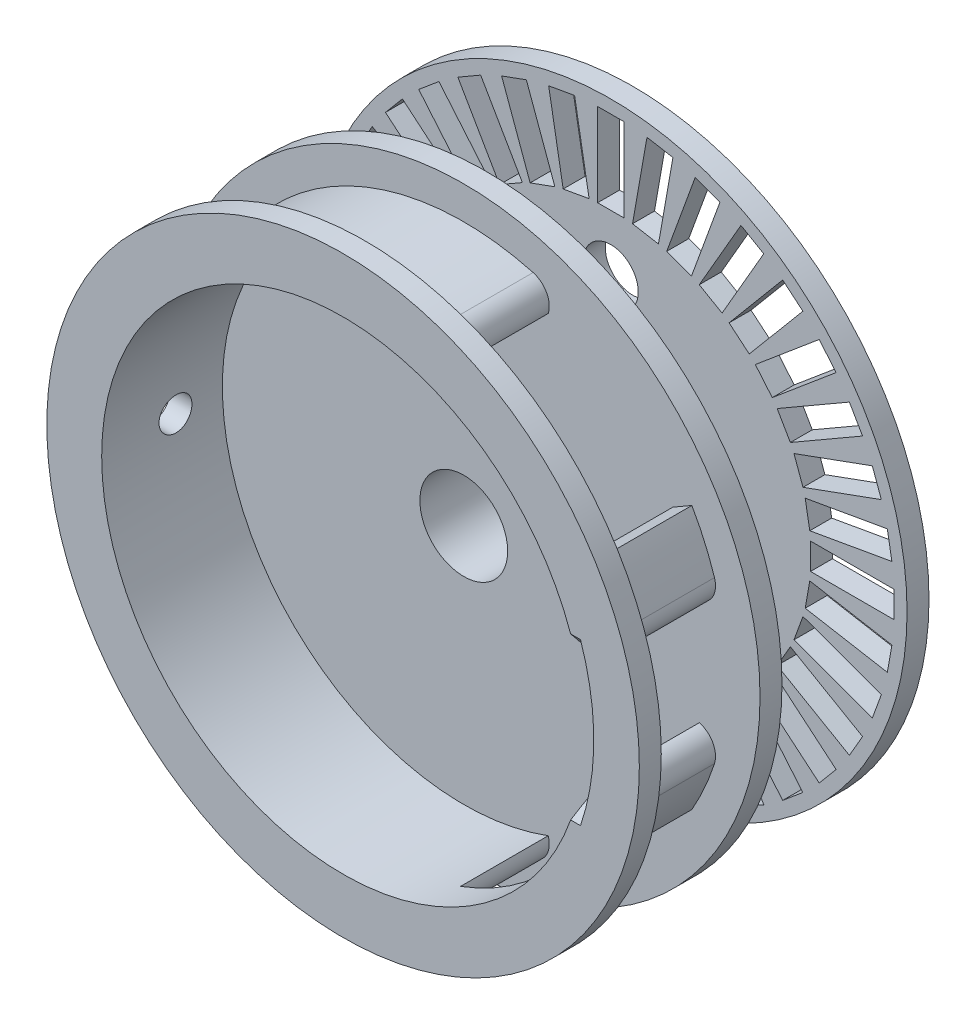
SolidWorks part; units mm, degrees
ref_plane "Front Plane" through (0, 0, 0) normal (0, 0, 1) x (1, 0, 0)
ref_plane "Top Plane" through (0, 0, 0) normal (0, 1, 0) x (1, 0, 0)
ref_plane "Right Plane" through (0, 0, 0) normal (1, 0, 0) x (0, 0, -1)
sketch "Sketch1" plane through (0, 0, 0) normal (0, 0, 1) x (1, 0, 0)
  line L0 (2.1711, 8.8576) -> (0.9893, 9.0659)
  line L1 (0.6, 9.1) -> (-0.6, 9.1)
  line L2 (0.6, 9.1) -> (0.6, 12.9)
  line L3 (0.6, 12.9) -> (-0.6, 12.9)
  line L4 (-0.6, 9.1) -> (-0.6, 12.9)
  line L5 (0.6, 9.1) -> (-0.6, 12.9) construction
  line L6 (0.6, 12.9) -> (-0.6, 9.1) construction
  line L7 (0.9893, 9.0659) -> (1.6492, 12.8082)
  line L8 (2.1711, 8.8576) -> (2.8309, 12.5998)
  line L9 (2.8309, 12.5998) -> (1.6492, 12.8082)
  line L10 (3.6762, 8.346) -> (2.5486, 8.7564)
  line L11 (2.5486, 8.7564) -> (3.8482, 12.3272)
  line L12 (3.6762, 8.346) -> (4.9759, 11.9168)
  line L13 (4.9759, 11.9168) -> (3.8482, 12.3272)
  line L14 (5.0696, 7.5808) -> (4.0304, 8.1808)
  line L15 (4.0304, 8.1808) -> (5.9304, 11.4717)
  line L16 (5.0696, 7.5808) -> (6.9696, 10.8717)
  line L17 (6.9696, 10.8717) -> (5.9304, 11.4717)
  line L18 (6.309, 6.5853) -> (5.3897, 7.3567)
  line L19 (5.3897, 7.3567) -> (7.8323, 10.2676)
  line L20 (6.309, 6.5853) -> (8.7516, 9.4963)
  line L21 (8.7516, 9.4963) -> (7.8323, 10.2676)
  line L22 (7.3567, 5.3897) -> (6.5853, 6.309)
  line L23 (6.5853, 6.309) -> (9.4963, 8.7516)
  line L24 (7.3567, 5.3897) -> (10.2676, 7.8323)
  line L25 (10.2676, 7.8323) -> (9.4963, 8.7516)
  line L26 (8.1808, 4.0304) -> (7.5808, 5.0696)
  line L27 (7.5808, 5.0696) -> (10.8717, 6.9696)
  line L28 (8.1808, 4.0304) -> (11.4717, 5.9304)
  line L29 (11.4717, 5.9304) -> (10.8717, 6.9696)
  line L30 (8.7564, 2.5486) -> (8.346, 3.6762)
  line L31 (8.346, 3.6762) -> (11.9168, 4.9759)
  line L32 (8.7564, 2.5486) -> (12.3272, 3.8482)
  line L33 (12.3272, 3.8482) -> (11.9168, 4.9759)
  line L34 (9.0659, 0.9893) -> (8.8576, 2.1711)
  line L35 (8.8576, 2.1711) -> (12.5998, 2.8309)
  line L36 (9.0659, 0.9893) -> (12.8082, 1.6492)
  line L37 (12.8082, 1.6492) -> (12.5998, 2.8309)
  line L38 (9.1, -0.6) -> (9.1, 0.6)
  line L39 (9.1, 0.6) -> (12.9, 0.6)
  line L40 (9.1, -0.6) -> (12.9, -0.6)
  line L41 (12.9, -0.6) -> (12.9, 0.6)
  line L42 (8.8576, -2.1711) -> (9.0659, -0.9893)
  line L43 (9.0659, -0.9893) -> (12.8082, -1.6492)
  line L44 (8.8576, -2.1711) -> (12.5998, -2.8309)
  line L45 (12.5998, -2.8309) -> (12.8082, -1.6492)
  line L46 (8.346, -3.6762) -> (8.7564, -2.5486)
  line L47 (8.7564, -2.5486) -> (12.3272, -3.8482)
  line L48 (8.346, -3.6762) -> (11.9168, -4.9759)
  line L49 (11.9168, -4.9759) -> (12.3272, -3.8482)
  line L50 (7.5808, -5.0696) -> (8.1808, -4.0304)
  line L51 (8.1808, -4.0304) -> (11.4717, -5.9304)
  line L52 (7.5808, -5.0696) -> (10.8717, -6.9696)
  line L53 (10.8717, -6.9696) -> (11.4717, -5.9304)
  line L54 (6.5853, -6.309) -> (7.3567, -5.3897)
  line L55 (7.3567, -5.3897) -> (10.2676, -7.8323)
  line L56 (6.5853, -6.309) -> (9.4963, -8.7516)
  line L57 (9.4963, -8.7516) -> (10.2676, -7.8323)
  line L58 (5.3897, -7.3567) -> (6.309, -6.5853)
  line L59 (6.309, -6.5853) -> (8.7516, -9.4963)
  line L60 (5.3897, -7.3567) -> (7.8323, -10.2676)
  line L61 (7.8323, -10.2676) -> (8.7516, -9.4963)
  line L62 (4.0304, -8.1808) -> (5.0696, -7.5808)
  line L63 (5.0696, -7.5808) -> (6.9696, -10.8717)
  line L64 (4.0304, -8.1808) -> (5.9304, -11.4717)
  line L65 (5.9304, -11.4717) -> (6.9696, -10.8717)
  line L66 (2.5486, -8.7564) -> (3.6762, -8.346)
  line L67 (3.6762, -8.346) -> (4.9759, -11.9168)
  line L68 (2.5486, -8.7564) -> (3.8482, -12.3272)
  line L69 (3.8482, -12.3272) -> (4.9759, -11.9168)
  line L70 (0.9893, -9.0659) -> (2.1711, -8.8576)
  line L71 (2.1711, -8.8576) -> (2.8309, -12.5998)
  line L72 (0.9893, -9.0659) -> (1.6492, -12.8082)
  line L73 (1.6492, -12.8082) -> (2.8309, -12.5998)
  line L74 (-0.6, -9.1) -> (0.6, -9.1)
  line L75 (0.6, -9.1) -> (0.6, -12.9)
  line L76 (-0.6, -9.1) -> (-0.6, -12.9)
  line L77 (-0.6, -12.9) -> (0.6, -12.9)
  line L78 (-2.1711, -8.8576) -> (-0.9893, -9.0659)
  line L79 (-0.9893, -9.0659) -> (-1.6492, -12.8082)
  line L80 (-2.1711, -8.8576) -> (-2.8309, -12.5998)
  line L81 (-2.8309, -12.5998) -> (-1.6492, -12.8082)
  line L82 (-3.6762, -8.346) -> (-2.5486, -8.7564)
  line L83 (-2.5486, -8.7564) -> (-3.8482, -12.3272)
  line L84 (-3.6762, -8.346) -> (-4.9759, -11.9168)
  line L85 (-4.9759, -11.9168) -> (-3.8482, -12.3272)
  line L86 (-5.0696, -7.5808) -> (-4.0304, -8.1808)
  line L87 (-4.0304, -8.1808) -> (-5.9304, -11.4717)
  line L88 (-5.0696, -7.5808) -> (-6.9696, -10.8717)
  line L89 (-6.9696, -10.8717) -> (-5.9304, -11.4717)
  line L90 (-6.309, -6.5853) -> (-5.3897, -7.3567)
  line L91 (-5.3897, -7.3567) -> (-7.8323, -10.2676)
  line L92 (-6.309, -6.5853) -> (-8.7516, -9.4963)
  line L93 (-8.7516, -9.4963) -> (-7.8323, -10.2676)
  line L94 (-7.3567, -5.3897) -> (-6.5853, -6.309)
  line L95 (-6.5853, -6.309) -> (-9.4963, -8.7516)
  line L96 (-7.3567, -5.3897) -> (-10.2676, -7.8323)
  line L97 (-10.2676, -7.8323) -> (-9.4963, -8.7516)
  line L98 (-8.1808, -4.0304) -> (-7.5808, -5.0696)
  line L99 (-7.5808, -5.0696) -> (-10.8717, -6.9696)
  line L100 (-8.1808, -4.0304) -> (-11.4717, -5.9304)
  line L101 (-11.4717, -5.9304) -> (-10.8717, -6.9696)
  line L102 (-8.7564, -2.5486) -> (-8.346, -3.6762)
  line L103 (-8.346, -3.6762) -> (-11.9168, -4.9759)
  line L104 (-8.7564, -2.5486) -> (-12.3272, -3.8482)
  line L105 (-12.3272, -3.8482) -> (-11.9168, -4.9759)
  line L106 (-9.0659, -0.9893) -> (-8.8576, -2.1711)
  line L107 (-8.8576, -2.1711) -> (-12.5998, -2.8309)
  line L108 (-9.0659, -0.9893) -> (-12.8082, -1.6492)
  line L109 (-12.8082, -1.6492) -> (-12.5998, -2.8309)
  line L110 (-9.1, 0.6) -> (-9.1, -0.6)
  line L111 (-9.1, -0.6) -> (-12.9, -0.6)
  line L112 (-9.1, 0.6) -> (-12.9, 0.6)
  line L113 (-12.9, 0.6) -> (-12.9, -0.6)
  line L114 (-8.8576, 2.1711) -> (-9.0659, 0.9893)
  line L115 (-9.0659, 0.9893) -> (-12.8082, 1.6492)
  line L116 (-8.8576, 2.1711) -> (-12.5998, 2.8309)
  line L117 (-12.5998, 2.8309) -> (-12.8082, 1.6492)
  line L118 (-8.346, 3.6762) -> (-8.7564, 2.5486)
  line L119 (-8.7564, 2.5486) -> (-12.3272, 3.8482)
  line L120 (-8.346, 3.6762) -> (-11.9168, 4.9759)
  line L121 (-11.9168, 4.9759) -> (-12.3272, 3.8482)
  line L122 (-7.5808, 5.0696) -> (-8.1808, 4.0304)
  line L123 (-8.1808, 4.0304) -> (-11.4717, 5.9304)
  line L124 (-7.5808, 5.0696) -> (-10.8717, 6.9696)
  line L125 (-10.8717, 6.9696) -> (-11.4717, 5.9304)
  line L126 (-6.5853, 6.309) -> (-7.3567, 5.3897)
  line L127 (-7.3567, 5.3897) -> (-10.2676, 7.8323)
  line L128 (-6.5853, 6.309) -> (-9.4963, 8.7516)
  line L129 (-9.4963, 8.7516) -> (-10.2676, 7.8323)
  line L130 (-5.3897, 7.3567) -> (-6.309, 6.5853)
  line L131 (-6.309, 6.5853) -> (-8.7516, 9.4963)
  line L132 (-5.3897, 7.3567) -> (-7.8323, 10.2676)
  line L133 (-7.8323, 10.2676) -> (-8.7516, 9.4963)
  line L134 (-4.0304, 8.1808) -> (-5.0696, 7.5808)
  line L135 (-5.0696, 7.5808) -> (-6.9696, 10.8717)
  line L136 (-4.0304, 8.1808) -> (-5.9304, 11.4717)
  line L137 (-5.9304, 11.4717) -> (-6.9696, 10.8717)
  line L138 (-2.5486, 8.7564) -> (-3.6762, 8.346)
  line L139 (-3.6762, 8.346) -> (-4.9759, 11.9168)
  line L140 (-2.5486, 8.7564) -> (-3.8482, 12.3272)
  line L141 (-3.8482, 12.3272) -> (-4.9759, 11.9168)
  line L142 (-0.9893, 9.0659) -> (-2.1711, 8.8576)
  line L143 (-2.1711, 8.8576) -> (-2.8309, 12.5998)
  line L144 (-0.9893, 9.0659) -> (-1.6492, 12.8082)
  line L145 (-1.6492, 12.8082) -> (-2.8309, 12.5998)
  circle A0 centre (0, 0) radius 13.5
  circle A1 centre (0, 0) radius 2
  point P3 (0, 11)
  dimension "D2" = 27
  dimension "D5" = 4
  dimension "D1" = 1.2
  dimension "D3" = 3.8
  dimension "D6" = 12.9
  dimension "D4" = 36
extrude "Boss-Extrude1" add sketch "Sketch1" along normal blind 1
sketch "Sketch2" plane through (0, 0, 1) normal (0, 0, 1) x (1, 0, 0)
  circle A0 centre (0, 0) radius 5
  circle A1 centre (0, 0) radius 2
  circle A2 centre (0, 0) radius 6.25 construction
  circle A4 centre (0, 0) radius 2 construction
  dimension "D1" = 3
  dimension "D3" = 12.5
extrude "Boss-Extrude2" add sketch "Sketch2" along normal blind 5.7
sketch "Sketch3" plane through (0, 0, 6.7) normal (0, 0, 1) x (1, 0, 0)
  circle A0 centre (0, 0) radius 2
  circle A1 centre (0, 0) radius 12
  circle A2 centre (0, 0) radius 2 construction
  dimension "D1" = 24
extrude "Boss-Extrude3" add sketch "Sketch3" along normal blind 1
sketch "Sketch4" plane through (0, 0, 7.7) normal (0, 0, 1) x (1, 0, 0)
  line L1 (8.358, -2.4) -> (13.642, -2.4)
  line L2 (8.358, -2.4) -> (8.358, 2.4)
  line L3 (8.358, 2.4) -> (13.642, 2.4)
  line L4 (13.642, -2.4) -> (13.642, 2.4)
  line L5 (8.358, -2.4) -> (13.642, 2.4) construction
  line L6 (8.358, 2.4) -> (13.642, -2.4) construction
  circle A0 centre (0, 0) radius 12
  circle A1 centre (0, 0) radius 11
  circle A2 centre (0, 0) radius 12 construction
  point P6 (11, 0)
  circle M2 centre (0, 0) radius 12
  dimension "D1" = 1
  dimension "D2" = 4.8
extrude "Boss-Extrude4" add sketch "Sketch4" along normal blind 5.5 contours A1 L3 L1 M2 region at (11.2463, -2.7377, 7.7)
sketch "Sketch5" plane through (0, 0, 7.7) normal (0, 0, 1) x (1, 0, 0)
  line L0 (0, 0) -> (15.9926, 9.2333)
  line L1 (15.9926, 9.2333) -> (12.4926, 15.2955)
  line L2 (12.4926, 15.2955) -> (-1.9963, 6.9303)
  line L3 (-1.9963, 6.9303) -> (0, 0)
  line L4 (0, 0) -> (19.351, 0) construction
  line L5 (-1.9963, -6.9303) -> (0, 0)
  line L6 (12.4926, -15.2955) -> (-1.9963, -6.9303)
  line L7 (15.9926, -9.2333) -> (12.4926, -15.2955)
  line L8 (0, 0) -> (15.9926, -9.2333)
  circle A0 centre (0, 0) radius 11
  circle A1 centre (0, 0) radius 13.5
  arc A2 (10.735, 2.4) -> (10.735, -2.4) centre (0, 0) ccw construction
  arc M9 (10.735, 2.4) -> (10.735, -2.4) centre (0, 0) ccw
  dimension "D1" = 7
  dimension "D2" = 30
extrude "Cut-Extrude1" cut sketch "Sketch5" along normal blind 4 contours L0 A1 L2 M9 | L6 A1 L8 M9 region at (8.1499, 8.8784, 7.7) region at (8.1499, -8.8784, 7.7)
fillet "Fillet1" radius 1 2 edges at (11.7576, 2.4, 10.45) (11.7576, -2.4, 10.45)
sketch "Sketch6" plane through (0, 0, 0) normal (1, 0, 0) x (0, 0, -1)
  line L0 (-1, 13.5) -> (-1, -13.5) construction
  line L1 (-6.8276, -5) -> (-1, -5)
  line L2 (-6.8276, -5) -> (-6.8276, 5)
  line L3 (-6.8276, 5) -> (-1, 5)
  line L4 (-1, -5) -> (-1, 5)
  line L5 (-6.8276, -5) -> (-1, 5) construction
  line L6 (-6.8276, 5) -> (-1, -5) construction
  line L7 (-1, 5) -> (-6.7, 5) construction
  line L8 (-6.7, -5) -> (-1, -5) construction
  circle A0 centre (-3.9138, 0) radius 1
  point P2 (-3.9138, 0)
  dimension "D1" = 2
extrude "Cut-Extrude2" [suppressed] cut sketch "Sketch6" against normal blind 4 and the other way blind 4 contours A0
fillet "Fillet2" radius 1 2 edges at (4.941, 10.9356, 9.7) (4.941, -10.9356, 9.7)
sketch "Sketch7" plane through (0, 0, 0) normal (0, 0, -1) x (-1, 0, 0)
  circle A0 centre (0, 6.5) radius 1.25
  dimension "D1" = 2.5
  dimension "D2" = 6.5
extrude "Cut-Extrude3" cut sketch "Sketch7" against normal blind 4
sketch "Sketch9" plane through (0, 0, 0) normal (1, 0, 0) x (0, 0, -1)
  line L0 (-11.7, 6) -> (-7.7, 6) construction
  line L1 (-13.2, 0) -> (-16.6587, 0) construction
  line L2 (-13.2, 11) -> (-13.2, -11) construction
  line L3 (-10.8193, 1.9476) -> (-10.8193, -1.9476)
  circle A0 centre (-9.7, 6) radius 4.2041
  circle A1 centre (-9.7, -6) radius 4.2041
  circle A2 centre (-10.8193, 0) radius 5.3426
extrude "Cut-Extrude4" cut sketch "Sketch9" along normal blind 16 contours A0 A2 A1 L3 region at (0, 0, 13.5585)
sketch "Sketch10" plane through (0, 0, 0) normal (0, 1, 0) x (1, 0, 0)
  line L0 (-12, -9.95) -> (-17.7584, -9.95) construction
  line L5 (-12, -6.7) -> (-12, -13.2) construction
  line L10 (13.5, -6.7) -> (13.5, -7.7)
  line L11 (11.4247, -13.2) -> (13.5, -13.2)
  line L12 (11.4247, -13.2) -> (11.4247, -12.2)
  line L13 (11.4247, -12.2) -> (13.5, -12.2)
  line L14 (13.5, -13.2) -> (13.5, -12.2)
  line L15 (11.4247, -7.7) -> (13.5, -7.7)
  line L16 (11.4247, -6.7) -> (11.4247, -7.7)
  line L17 (11.4247, -6.7) -> (13.5, -6.7)
  line L18 (13.5, 0) -> (13.5, -5.1753) construction
  line L19 (13.5, 0) -> (-13.5, 0) construction
  line L20 (13.5, -1) -> (13.5, 0) construction
  line L21 (0, 0) -> (0, 9.3712) construction
  dimension "D1" = 1
revolve "Revolve1" add sketch "Sketch10" angle 360 about L21
sketch "Sketch11" plane through (0, 0, 0) normal (1, 0, 0) x (0, 0, -1)
  circle A0 centre (-9.8371, 0) radius 0.75
  point P2 (0, 0)
  dimension "D1" = 1.5
extrude "Cut-Extrude6" cut sketch "Sketch11" against normal blind 100
equation "\"|.6\"=1.2"
